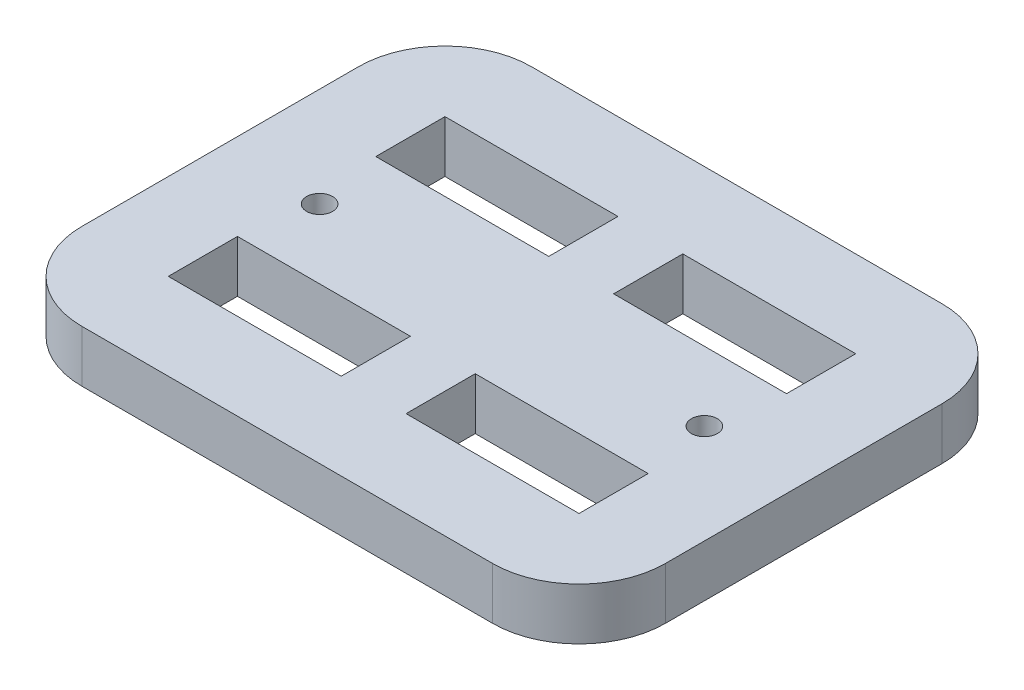
SolidWorks part; units mm, degrees
ref_plane "Front Plane" through (0, 0, 0) normal (0, 0, 1) x (1, 0, 0)
ref_plane "Top Plane" through (0, 0, 0) normal (0, 1, 0) x (1, 0, 0)
ref_plane "Right Plane" through (0, 0, 0) normal (1, 0, 0) x (0, 0, -1)
sketch "Sketch1" plane through (0, 0, 0) normal (0, 1, 0) x (1, 0, 0)
  line L0 (-20.75, 0) -> (0, 0) construction
  line L1 (-33.75, 26) -> (0, 26)
  line L2 (-33.75, 26) -> (-33.75, -26)
  line L3 (-33.75, 0) -> (-23.75, 0) construction
  line L4 (0, 26) -> (0, -26)
  line L5 (-33.75, 26) -> (0, 0) construction
  line L6 (-33.75, 0) -> (0, 26) construction
  line L7 (-23.75, 16) -> (-3.75, 16)
  line L8 (-23.75, 16) -> (-23.75, 8)
  line L9 (-23.75, 8) -> (-3.75, 8)
  line L10 (-3.75, 16) -> (-3.75, 8)
  line L11 (-23.75, 16) -> (-3.75, 8) construction
  line L12 (-23.75, 8) -> (-3.75, 16) construction
  line L13 (-23.75, -8) -> (-3.75, -16) construction
  line L14 (-23.75, -16) -> (-3.75, -8) construction
  line L15 (-33.75, 0) -> (0, -26) construction
  line L16 (-33.75, -26) -> (0, 0) construction
  line L17 (-3.75, -16) -> (-3.75, -8)
  line L18 (-23.75, -8) -> (-3.75, -8)
  line L19 (-23.75, -16) -> (-23.75, -8)
  line L20 (-23.75, -16) -> (-3.75, -16)
  line L21 (-33.75, -26) -> (0, -26)
  circle A0 centre (-22.25, 0) radius 1.5
  point P0 (-16.875, 13)
  point P6 (-13.75, 12)
  point P21 (-13.75, -12)
  point P22 (-16.875, -13)
  dimension "D1" = 1.5
  dimension "D2" = 8
  dimension "D3" = 20
  dimension "D4" = 3.75
  dimension "D5" = 12
  dimension "D6" = 10
  dimension "D7" = 10
  dimension "D8" = 22.25
extrude "Boss-Extrude1" add sketch "Sketch1" along normal blind 6
fillet "Fillet1" radius 10 2 edges at (-33.75, 3, -26) (-33.75, 3, 26)
mirror "Mirror1" about plane through (0, 6, -26) normal (-1, 0, 0) of "Fillet1", "Boss-Extrude1"
equation "\"housing_t\"= \"housing_t_glob@troublemaker.Assembly\""
equation "\"M3_d\"= \"M3_d_laser@troublemaker.Assembly\""
equation "\"D1@Sketch1\"=\"M3_d\" / 2"
equation "\"D2@Sketch1\"=\"housing_t\" + 2"
equation "\"D5@Sketch1\"=2 * \"housing_t\""
equation "\"D1@Boss-Extrude1\"=\"housing_t\""
